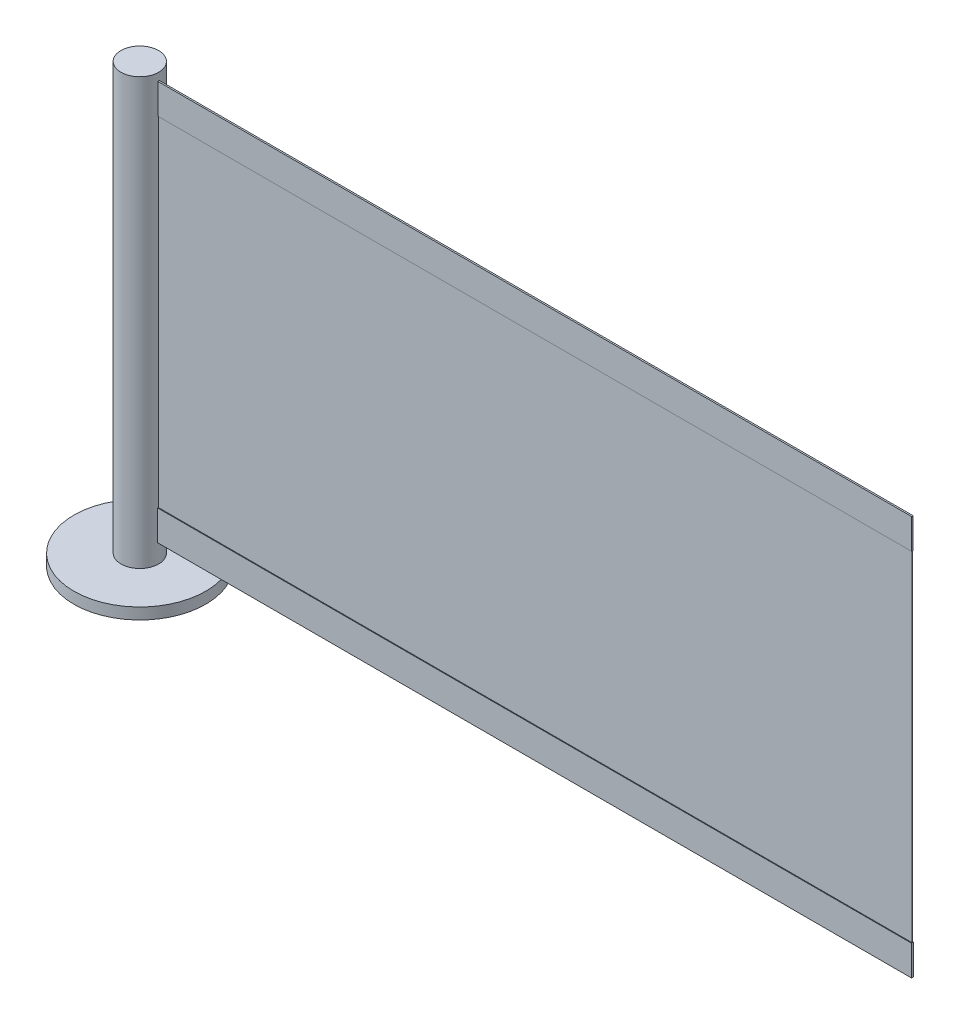
SolidWorks part; units mm, degrees
ref_plane "Front Plane" through (0, 0, 0) normal (0, 0, 1) x (1, 0, 0)
ref_plane "Top Plane" through (0, 0, 0) normal (0, 1, 0) x (1, 0, 0)
ref_plane "Right Plane" through (0, 0, 0) normal (1, 0, 0) x (0, 0, -1)
sketch "Sketch2" plane through (0, 0, 0) normal (0, 1, 0) x (1, 0, 0)
  circle A0 centre (0, 0) radius 175
extrude "Boss-Extrude1" add sketch "Sketch2" along normal blind 30
sketch "Sketch3" plane through (0, 30, 0) normal (0, 1, 0) x (1, 0, 0)
  circle A1 centre (0, 0) radius 50
extrude "Boss-Extrude2" add sketch "Sketch3" along normal blind 1110
sketch "Sketch7" plane through (0, 1140, 0) normal (0, 1, 0) x (1, 0, 0)
  line L0 (0, -0.5) -> (0, 0.5) construction
  line L2 (0, -0.5) -> (2050, -0.5)
  line L3 (0, -0.5) -> (0, 0.5)
  line L4 (0, 0.5) -> (2050, 0.5)
  line L5 (2050, -0.5) -> (2050, 0.5)
  point P5 (0, 0)
  dimension "D1" = 1
  dimension "D2" = 2050
extrude "Boss-Extrude3" add sketch "Sketch7" against normal blind 1060
sketch "Sketch8" plane through (0, 1140, 0) normal (0, 1, 0) x (1, 0, 0)
  line L0 (0, -2) -> (0, 2) construction
  line L2 (0, -2) -> (2050, -2)
  line L3 (0, -2) -> (0, 2)
  line L4 (0, 2) -> (2050, 2)
  line L5 (2050, -2) -> (2050, 2)
  point P4 (0, 0)
  dimension "D1" = 4
  dimension "D2" = 2050
extrude "Boss-Extrude4" add sketch "Sketch8" against normal blind 80
sketch3d "3DSketch2"
  line L0 (2050, 80, 0.5) -> (2050, 80, -0.5) construction
  line L1 (2050, 80, -0.5) -> (49.9975, 80, -0.5) construction
sketch "Sketch11" plane through (0, 80, 0) normal (0, -1, 0) x (-1, 0, 0)
  line L0 (-2050, -2.4692) -> (-2050, 2.4692) construction
  line L2 (-2050, -0.5) -> (-2050, 0.5) construction
  line L4 (-2050, -2.4692) -> (0, -2.4692)
  line L5 (-2050, -2.4692) -> (-2050, 2.4692)
  line L6 (-2050, 2.4692) -> (0, 2.4692)
  line L7 (0, -2.4692) -> (0, 2.4692)
  point P3 (-2050, 0)
  dimension "D1" = 2050
extrude "Boss-Extrude5" add sketch "Sketch11" against normal blind 80
sketch "Sketch12" plane through (0, 1140, 0) normal (0, 1, 0) x (1, 0, 0)
  circle A0 centre (0, 0) radius 50
extrude "Boss-Extrude6" add sketch "Sketch12" along normal blind 20
